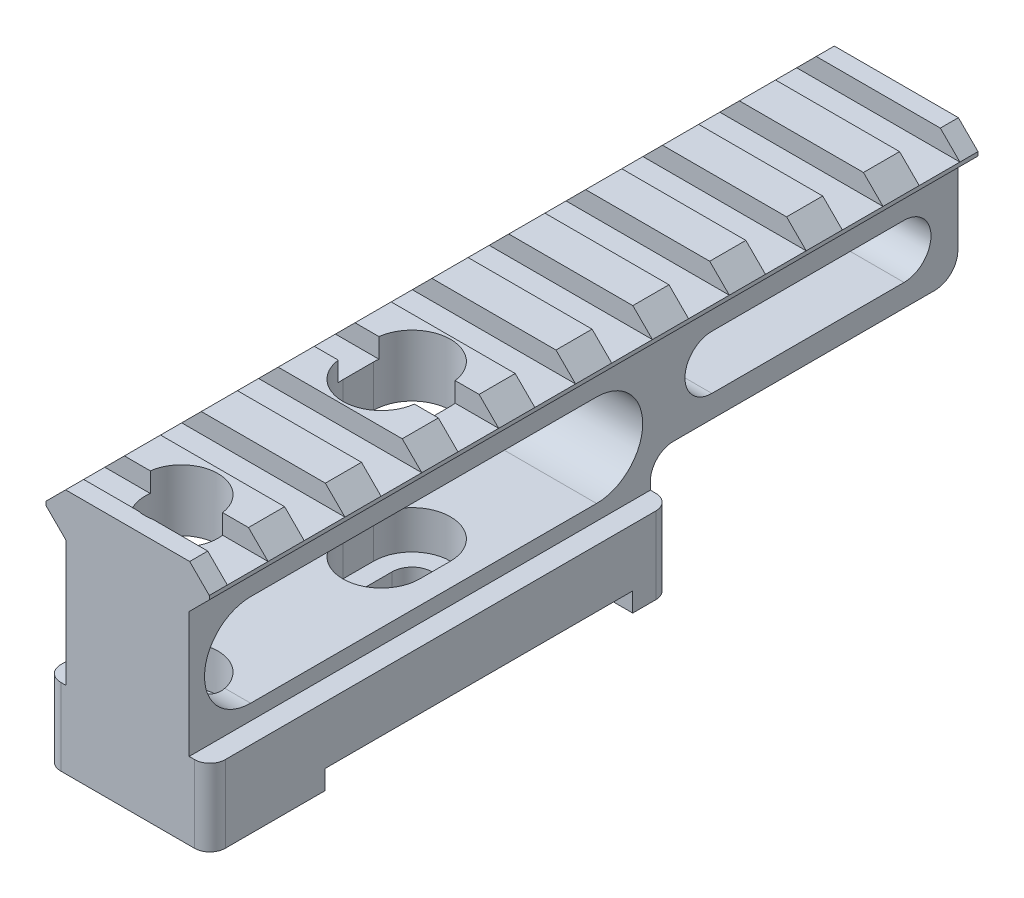
SolidWorks part; units mm, degrees
ref_plane "Front Plane" through (0, 0, 0) normal (0, 0, 1) x (1, 0, 0)
ref_plane "Top Plane" through (0, 0, 0) normal (0, 1, 0) x (1, 0, 0)
ref_plane "Right Plane" through (0, 0, 0) normal (1, 0, 0) x (0, 0, -1)
sketch "Sketch2" plane through (0, 0, 0) normal (0, 0, 1) x (1, 0, 0)
  line L0 (-8, 11) -> (8, 11)
  line L1 (8, 11) -> (8, 37.33)
  line L2 (8, 37.33) -> (10.62, 39.95)
  line L3 (10.62, 39.95) -> (10.62, 40.45)
  line L4 (10.62, 40.45) -> (8.07, 43)
  line L5 (8.07, 43) -> (-8.07, 43)
  line L6 (-8.07, 43) -> (-10.62, 40.45)
  line L7 (-10.62, 40.45) -> (-10.62, 39.95)
  line L8 (-10.62, 39.95) -> (-8, 37.33)
  line L9 (-8, 37.33) -> (-8, 11)
  line L10 (0, 43) -> (0, 11) construction
  line L12 (-9.5, 41.57) -> (9.5, 41.57) construction
  line L13 (-9.5, 41.57) -> (-9.5, 38.83) construction
  line L14 (-9.5, 38.83) -> (9.5, 38.83) construction
  line L15 (9.5, 41.57) -> (9.5, 38.83) construction
  dimension "D1" = 16
  dimension "D2" = 0.5
  dimension "D3" = 0.5
  dimension "D4" = 45
  dimension "D5" = 45
  dimension "D6" = 19
  dimension "D7" = 32
  dimension "D8" = 2.74
  dimension "D9" = 4.17
  dimension "D10" = 21.24
  dimension "D11" = 11
extrude "Boss-Extrude1" add sketch "Sketch2" along normal blind 100 from offset 530
sketch "Sketch3" plane through (0, 0, 630) normal (0, 0, -1) x (-1, 0, 0)
  line L0 (0, 21) -> (0, 11) construction
  line L1 (-10.7, 11) -> (10.7, 11)
  line L2 (-10.7, 11) -> (-10.7, 21)
  line L3 (-10.7, 21) -> (10.7, 21)
  line L4 (10.7, 11) -> (10.7, 21)
  line L5 (8, 11) -> (-8, 11) construction
  dimension "D1" = 10
  dimension "D2" = 21.4
extrude "Boss-Extrude2" add sketch "Sketch3" along normal blind 60
sketch "Sketch4" plane through (0, 11, 0) normal (0, -1, 0) x (1, 0, 0)
  line L0 (-10.7, 575) -> (10.7, 575)
  line L1 (-10.7, 630) -> (10.7, 630) construction
  line L4 (-8, 530) -> (8, 530)
  line L5 (10.7, 570) -> (10.7, 630)
  line L6 (10.7, 630) -> (-10.7, 630)
  line L7 (-10.7, 630) -> (-10.7, 570)
  line L8 (-8, 530) -> (8, 530)
  line L9 (10.7, 575) -> (10.7, 615)
  line L11 (-10.7, 615) -> (-10.7, 575)
  line L17 (-8, 570) -> (-8, 530)
  line L18 (-8, 570) -> (-8, 530)
  line L19 (10.7, 615) -> (-10.7, 615)
  line L21 (-10.7, 570) -> (-8, 570)
  line L23 (8, 530) -> (8, 570)
  line L24 (8, 530) -> (8, 570)
  line L25 (-10.7, 570) -> (-8, 570)
  line L26 (8, 570) -> (10.7, 570)
  line L27 (8, 570) -> (10.7, 570)
  dimension "D2" = 15
  dimension "D3" = 40
  dimension "D1" = 0
extrude "Cut-Extrude1" cut sketch "Sketch4" against normal blind 2.5 contours L19 L11 L0 L9
sketch "Sketch5" plane through (8, 0, 0) normal (1, 0, 0) x (0, 0, -1)
  line L0 (-622, 29) -> (-577, 29) construction
  line L1 (-622, 35) -> (-577, 35)
  line L2 (-622, 23) -> (-577, 23)
  line L3 (-570, 21) -> (-630, 21) construction
  line L4 (-630, 21) -> (-630, 37.33) construction
  arc A0 (-622, 35) -> (-622, 23) centre (-622, 29) ccw
  arc A1 (-577, 23) -> (-577, 35) centre (-577, 29) ccw
  point P2 (-599.5, 29)
  dimension "D4" = 8
  dimension "D1" = 12
  dimension "D2" = 8
  dimension "D3" = 45
extrude "Cut-Extrude2" cut sketch "Sketch5" against normal blind 16
sketch "Sketch6" plane through (8, 0, 0) normal (1, 0, 0) x (0, 0, -1)
  line L0 (-570, 11) -> (-570, 21) construction
  line L1 (-530, 11) -> (-570, 11)
  line L2 (-530, 11) -> (-530, 25)
  line L3 (-530, 25) -> (-570, 25)
  line L4 (-570, 11) -> (-570, 25)
  dimension "D1" = 14
extrude "Cut-Extrude3" cut sketch "Sketch6" against normal blind 16
fillet "Fillet1" radius 3 1 edges at (0, 25, 570)
sketch "Sketch7" plane through (8, 0, 0) normal (1, 0, 0) x (0, 0, -1)
  line L0 (-562, 31.4) -> (-537, 31.4) construction
  line L1 (-562, 34.9) -> (-537, 34.9)
  line L2 (-562, 27.9) -> (-537, 27.9)
  line L3 (-530, 25) -> (-567, 25) construction
  line L4 (-530, 25) -> (-530, 37.33) construction
  arc A0 (-562, 34.9) -> (-562, 27.9) centre (-562, 31.4) ccw
  arc A1 (-537, 27.9) -> (-537, 34.9) centre (-537, 31.4) ccw
  point P2 (-549.5, 31.4)
  dimension "D1" = 7
  dimension "D2" = 6.4
  dimension "D3" = 25
  dimension "D4" = 7
extrude "Cut-Extrude4" cut sketch "Sketch7" against normal blind 16
fillet "Fillet2" radius 2 4 edges at (10.7, 16, 630) (10.7, 16, 570) (-10.7, 16, 630) (-10.7, 16, 570)
fillet "Fillet3" radius 3 1 edges at (0, 25, 530)
sketch "Sketch8" plane through (-10.62, 0, 0) normal (-1, 0, 0) x (0, 0, 1)
  line L0 (630, 43) -> (530, 43) construction
  line L1 (532.35, 43) -> (537.65, 43)
  line L2 (532.35, 43) -> (532.35, 40.45)
  line L3 (532.35, 40.45) -> (537.65, 40.45)
  line L4 (537.65, 43) -> (537.65, 40.45)
  line L5 (530, 43) -> (530, 40.45) construction
  dimension "D1" = 2.55
  dimension "D2" = 5.3
  dimension "D3" = 2.35
extrude "Cut-Extrude5" cut sketch "Sketch8" against normal blind 22
pattern_linear "LPattern1" count 10 spacing 10 along (0, 0, 1) of "Cut-Extrude5"
sketch "Sketch9" plane through (0, 43, 0) normal (0, 1, 0) x (1, 0, 0)
  line L0 (8.07, -630) -> (-8.07, -630) construction
  circle A0 centre (0, -623) radius 4.75
  dimension "D1" = 9.5
  dimension "D2" = 7
extrude "Cut-Extrude6" cut sketch "Sketch9" against normal blind 25
sketch "Sketch10" plane through (0, 18, 0) normal (0, 1, 0) x (1, 0, 0)
  circle A0 centre (0, -623) radius 2.6
  dimension "D1" = 5.2
extrude "Cut-Extrude7" cut sketch "Sketch10" against normal blind 15
sketch "Sketch11" plane through (0, 13.5, 0) normal (0, -1, 0) x (1, 0, 0)
  line L1 (0, 597) -> (0, 593) construction
  line L2 (2.6, 597) -> (2.6, 593)
  line L3 (-2.6, 597) -> (-2.6, 593)
  line L4 (-8.7, 630) -> (8.7, 630) construction
  arc A1 (2.6, 597) -> (-2.6, 597) centre (0, 597) ccw
  arc A2 (-2.6, 593) -> (2.6, 593) centre (0, 593) ccw
  point P7 (0, 595)
  dimension "D1" = 35
  dimension "D2" = 4
  dimension "D3" = 5.2
extrude "Cut-Extrude8" cut sketch "Sketch11" against normal blind 15
sketch "Sketch12" plane through (0, 23, 0) normal (0, 1, 0) x (1, 0, 0)
  line L0 (0, -597) -> (0, -593) construction
  line L1 (-5, -597) -> (-5, -593)
  line L2 (5, -597) -> (5, -593)
  line L3 (-8.7, -630) -> (8.7, -630) construction
  arc A0 (-5, -597) -> (5, -597) centre (0, -597) ccw
  arc A1 (5, -593) -> (-5, -593) centre (0, -593) ccw
  point P2 (0, -595)
  dimension "D1" = 4
  dimension "D2" = 10
  dimension "D3" = 35
extrude "Cut-Extrude9" cut sketch "Sketch12" along normal blind 22 and the other way blind 5
